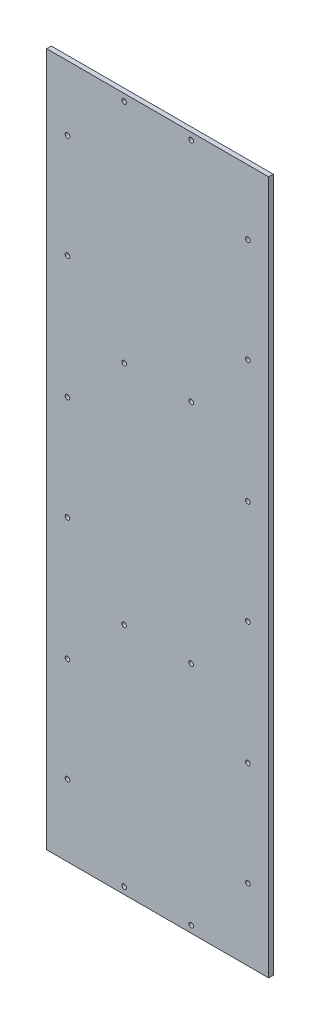
SolidWorks part; units mm, degrees
material "Alumina"
ref_plane "Front Plane" through (0, 0, 0) normal (0, 0, 1) x (1, 0, 0)
ref_plane "Top Plane" through (0, 0, 0) normal (0, 1, 0) x (1, 0, 0)
ref_plane "Right Plane" through (0, 0, 0) normal (1, 0, 0) x (0, 0, -1)
sketch "Sketch1" plane through (0, 0, 0) normal (0, 0, 1) x (1, 0, 0)
  line L1 (48, -150) -> (-48, -150)
  line L2 (48, -150) -> (48, 150)
  line L3 (48, 150) -> (-48, 150)
  line L4 (-48, -150) -> (-48, 150)
  line L5 (48, -150) -> (-48, 150) construction
  line L6 (48, 150) -> (-48, -150) construction
  point P0 (0, 0)
  dimension "D1" = 96
  dimension "D2" = 300
extrude "Boss-Extrude1" add sketch "Sketch1" along normal blind 2
sketch "Sketch2" plane through (0, 0, 2) normal (0, 0, 1) x (1, 0, 0)
  line L0 (-48, 150) -> (-48, -150) construction
  line L1 (48, 150) -> (-48, 150) construction
  line L2 (-48, -150) -> (48, -150) construction
  line L3 (48, -150) -> (48, 150) construction
  line L4 (0, -1.1) -> (0, 1.1) construction
  circle A0 centre (-39, 122) radius 1
  circle A1 centre (-39, 77) radius 1
  circle A2 centre (39, 122) radius 1
  circle A3 centre (39, 77) radius 1
  circle A4 centre (-39, 24) radius 1
  circle A5 centre (-39, -21) radius 1
  circle A6 centre (39, 24) radius 1
  circle A7 centre (39, -21) radius 1
  circle A8 centre (-39, -74) radius 1
  circle A9 centre (-39, -119) radius 1
  circle A10 centre (39, -74) radius 1
  circle A11 centre (39, -119) radius 1
  circle A13 centre (14.5, -147) radius 1
  circle A14 centre (-14.5, -147) radius 1
  circle A15 centre (-14.5, -49) radius 1
  circle A16 centre (14.5, -49) radius 1
  circle A17 centre (-14.5, 49) radius 1
  circle A18 centre (14.5, 49) radius 1
  circle A19 centre (-14.5, 147) radius 1
  circle A20 centre (14.5, 147) radius 1
  dimension "D1" = 2
  dimension "D3" = 28
  dimension "D4" = 2
  dimension "D6" = 9
  dimension "D10" = 2
  dimension "D11" = 33.5
  dimension "D13" = 3
  dimension "D15" = 9
  dimension "D2" = 9
  dimension "D5" = 45
  dimension "D9" = 31
  dimension "D14" = 9
  dimension "D16" = 3
  dimension "D7" = 2
  dimension "D8" = 3
  dimension "D12" = 4
extrude "Cut-Extrude1" cut sketch "Sketch2" against normal blind 10
